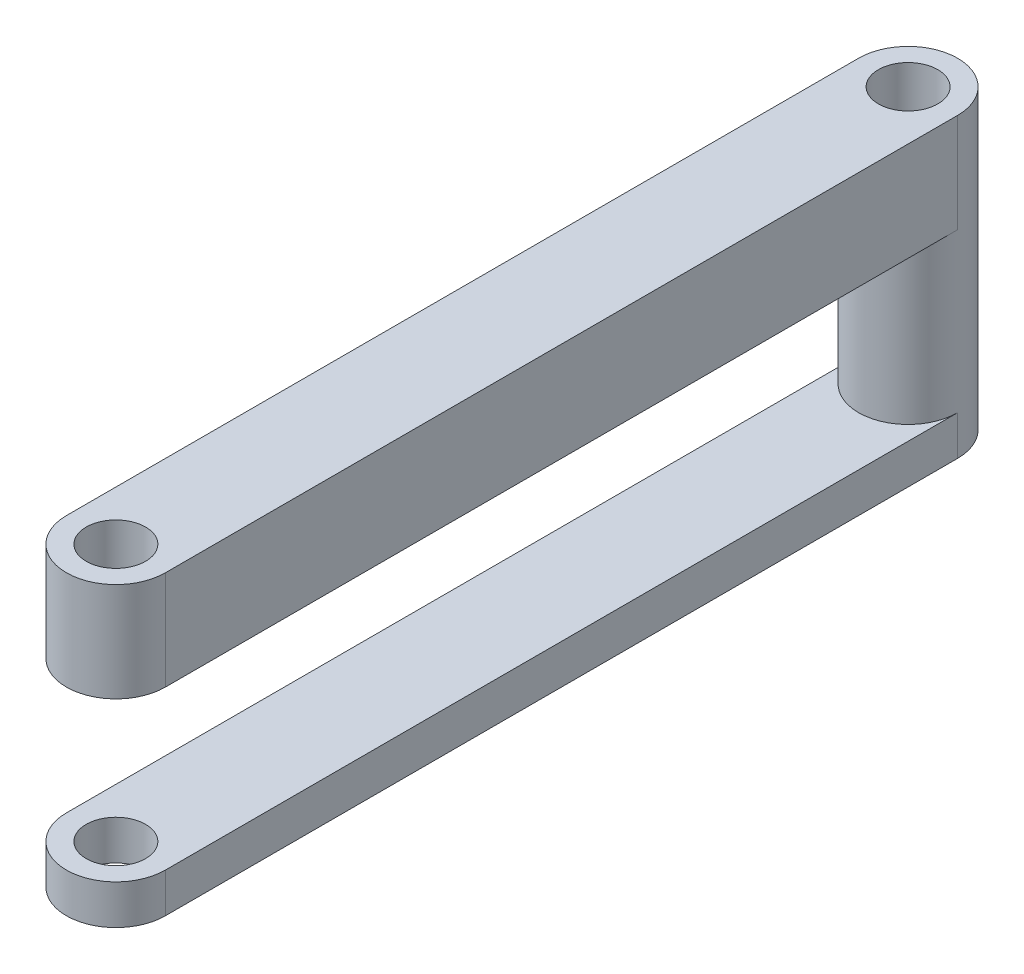
SolidWorks part; units mm, degrees
material "ABS"
ref_plane "Front Plane" through (0, 0, 0) normal (0, 0, 1) x (1, 0, 0)
ref_plane "Top Plane" through (0, 0, 0) normal (0, 1, 0) x (1, 0, 0)
ref_plane "Right Plane" through (0, 0, 0) normal (1, 0, 0) x (0, 0, -1)
sketch "Sketch1" plane through (0, 0, 0) normal (0, 1, 0) x (1, 0, 0)
  line L0 (0, 0) -> (0, -40) construction
  line L1 (2.5, 0) -> (2.5, -40)
  line L2 (-2.5, 0) -> (-2.5, -40)
  arc A0 (2.5, 0) -> (-2.5, 0) centre (0, 0) ccw
  arc A1 (-2.5, -40) -> (2.5, -40) centre (0, -40) ccw
  point P3 (0, -20)
  dimension "D2" = 2.5
  dimension "D1" = 40
extrude "Boss-Extrude1" add sketch "Sketch1" along normal blind 2 contours L1 A1 L2 A0
sketch "Sketch2" plane through (0, 2, 0) normal (0, 1, 0) x (1, 0, 0)
  circle A0 centre (0, 0) radius 2.5
  dimension "D1" = 5
extrude "Boss-Extrude2" add sketch "Sketch2" along normal blind 12
extrude "Boss-Extrude3" add sketch "Sketch1<3>" along normal blind 5 from offset 10
sketch "Sketch1<3>" plane through (0, 0, 0) normal (0, 1, 0) x (1, 0, 0) same geometry as "Sketch1"
hole_wizard "Ø3.0mm Clearance Dowel Hole1" positions "Sketch3" profile "Sketch4" hole size "Ø3.0" standard "ANSI Metric" end condition through all
sketch "Sketch3" plane through (0, 15, 0) normal (0, 1, 0) x (1, 0, 0)
  point P0 (0, 0)
  point P3 (0, -40)
sketch "Sketch4" plane through (0, 15, 0) normal (1, 0, 0) x (0, 0, 1)
  line L0 (0, 0) -> (0, 15)
  line L1 (0, 15) -> (1.5, 15)
  line L2 (1.5, 15) -> (1.5, 0)
  line L5 (1.5, 0) -> (0, 0)
  line L11 (0, -6.35) -> (0, 107.95) construction
  dimension "Thru Hole Dia." = 3
  dimension "Thru Hole Depth" = 15
